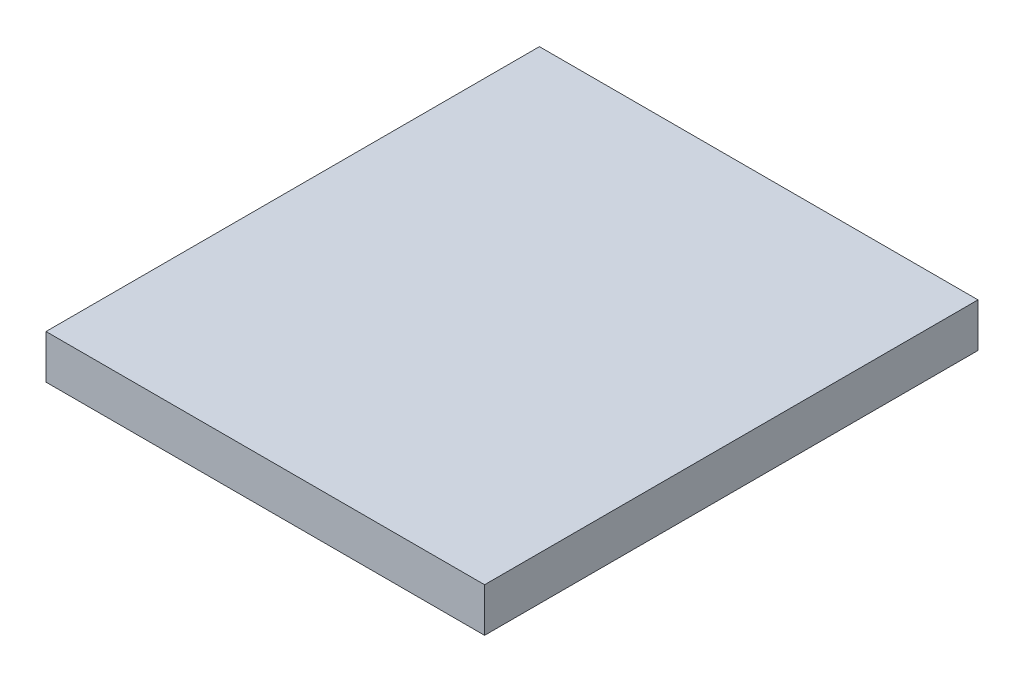
SolidWorks part; units mm, degrees
ref_plane "Front Plane" through (0, 0, 0) normal (0, 0, 1) x (1, 0, 0)
ref_plane "Top Plane" through (0, 0, 0) normal (0, 1, 0) x (1, 0, 0)
ref_plane "Right Plane" through (0, 0, 0) normal (1, 0, 0) x (0, 0, -1)
sketch "Sketch1" plane through (0, 0, 0) normal (0, 1, 0) x (1, 0, 0)
  line L0 (0, 0) -> (0, 45)
  line L1 (0, 45) -> (40, 45)
  line L2 (40, 45) -> (40, 0)
  line L3 (40, 0) -> (0, 0)
  dimension "D1" = 40
  dimension "D2" = 45
extrude "Boss-Extrude1" add sketch "Sketch1" along normal blind 4
